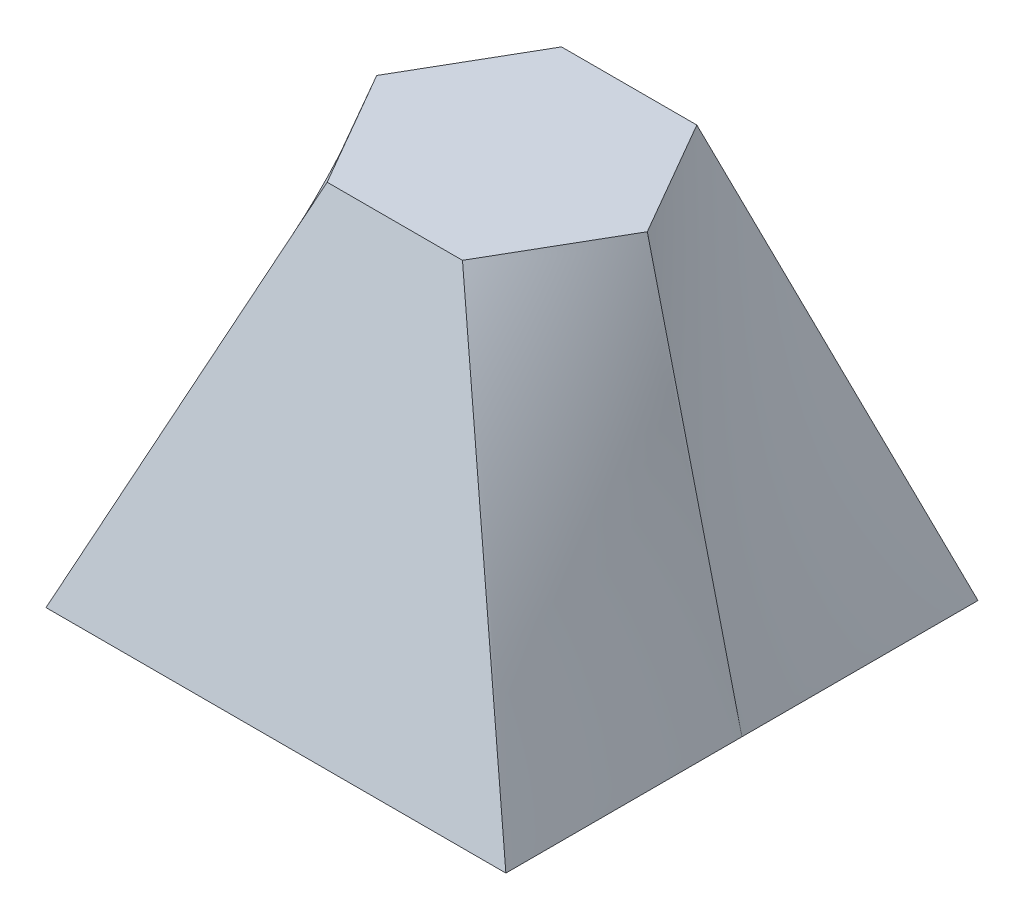
SolidWorks part; units mm, degrees
ref_plane "Front Plane" through (0, 0, 0) normal (0, 0, 1) x (1, 0, 0)
ref_plane "Top Plane" through (0, 0, 0) normal (0, 1, 0) x (1, 0, 0)
ref_plane "Right Plane" through (0, 0, 0) normal (1, 0, 0) x (0, 0, -1)
sketch "Sketch1" plane through (0, 0, 0) normal (0, 1, 0) x (1, 0, 0)
  line L0 (-44.9138, 0) -> (44.9138, 0) construction
  line L1 (-44.9138, -46.1106) -> (44.9138, -46.1106)
  line L2 (-44.9138, -46.1106) -> (-44.9138, 46.1106) construction
  line L3 (-44.9138, 46.1106) -> (44.9138, 46.1106)
  line L4 (44.9138, -46.1106) -> (44.9138, 46.1106) construction
  line L5 (-44.9138, -46.1106) -> (44.9138, 46.1106) construction
  line L6 (-44.9138, 46.1106) -> (44.9138, -46.1106) construction
  line L7 (-44.9138, 46.1106) -> (-44.9138, 0)
  line L8 (-44.9138, 0) -> (-44.9138, -46.1106)
  line L9 (44.9138, -46.1106) -> (44.9138, 0)
  line L10 (44.9138, 0) -> (44.9138, 46.1106)
  point P0 (0, 0)
ref_plane "Plane1" through (0, 76.2, 0) normal (0, 1, 0) x (1, 0, 0)
sketch "Sketch2" plane through (0, 76.2, 0) normal (0, 1, 0) x (1, 0, 0)
  line L0 (-44.9138, -46.1106) -> (44.9138, 46.1106) construction
  line L1 (26.43, 0) -> (13.215, 22.889)
  line L2 (13.215, 22.889) -> (-13.215, 22.889)
  line L3 (-13.215, 22.889) -> (-26.43, 0)
  line L4 (-26.43, 0) -> (-13.215, -22.889)
  line L5 (-13.215, -22.889) -> (13.215, -22.889)
  line L6 (13.215, -22.889) -> (26.43, 0)
  circle A0 centre (0, 0) radius 22.889 construction
loft "Loft1" add profiles "Sketch1", "Sketch2" connector at (44.9138, 0, 46.1106) connector at (13.215, 76.2, 22.889)
